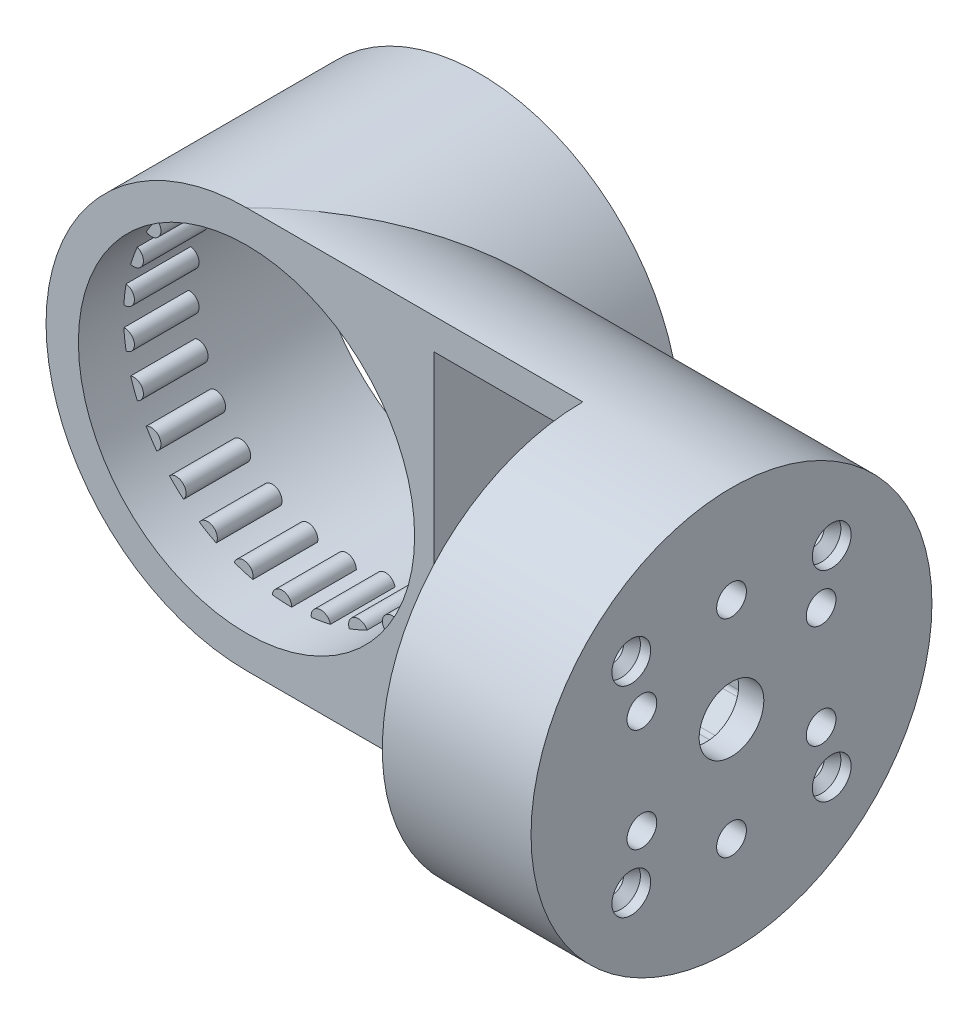
SolidWorks part; units mm, degrees
other "Markup1"
sketch "Sketch32" plane through (-30, -30, -30.9487) normal (-0.8677, -0.0705, -0.492) x (-0.0857, 0.9963, 0.0084)
ref_plane "Front Plane" through (0, 0, 0) normal (0, 0, 1) x (1, 0, 0)
ref_plane "Top Plane" through (0, 0, 0) normal (0, 1, 0) x (1, 0, 0)
ref_plane "Right Plane" through (0, 0, 0) normal (1, 0, 0) x (0, 0, -1)
sketch "Sketch3" plane through (0, 0, -2.9591) normal (0, 0, 1) x (1, 0, 0)
  circle A0 centre (0, 0) radius 31
  circle A1 centre (0, 0) radius 26
extrude "Boss-Extrude1" add sketch "Sketch3" along normal blind 7
sketch "Sketch4" plane through (0, 0, 4.0409) normal (0, 0, 1) x (1, 0, 0)
  line L0 (0, 0) -> (26, 0) construction
  circle A0 centre (0, 0) radius 26
  circle A1 centre (0, 0) radius 31
extrude "Boss-Extrude2" add sketch "Sketch4" along normal blind 10
sketch "Sketch5" plane through (0, 0, 4.0513) normal (0, 0, 1) x (1, 0, 0)
  line L0 (0, 0) -> (26, 0) construction
  circle A0 centre (0, 0) radius 26 construction
  circle A1 centre (26, 0) radius 1.5
  circle A2 centre (25.2992, -5.996) radius 1.5
  circle A3 centre (23.2344, -11.6688) radius 1.5
  circle A4 centre (19.9172, -16.7125) radius 1.5
  circle A5 centre (15.5261, -20.8552) radius 1.5
  circle A6 centre (10.2981, -23.8736) radius 1.5
  circle A7 centre (4.5149, -25.605) radius 1.5
  circle A8 centre (-1.5118, -25.956) radius 1.5
  circle A9 centre (-7.4569, -24.9077) radius 1.5
  circle A10 centre (-13, -22.5167) radius 1.5
  circle A11 centre (-17.8423, -18.9117) radius 1.5
  circle A12 centre (-21.7227, -14.2872) radius 1.5
  circle A13 centre (-24.432, -8.8925) radius 1.5
  circle A14 centre (-25.8242, -3.0184) radius 1.5
  circle A15 centre (-25.8242, 3.0184) radius 1.5
  circle A16 centre (-24.432, 8.8925) radius 1.5
  circle A17 centre (-21.7227, 14.2872) radius 1.5
  circle A18 centre (-17.8423, 18.9117) radius 1.5
  circle A19 centre (-13, 22.5167) radius 1.5
  circle A20 centre (-7.4569, 24.9077) radius 1.5
  circle A21 centre (-1.5118, 25.956) radius 1.5
  circle A22 centre (4.5149, 25.605) radius 1.5
  circle A23 centre (10.2981, 23.8736) radius 1.5
  circle A24 centre (15.5261, 20.8552) radius 1.5
  circle A25 centre (19.9172, 16.7125) radius 1.5
  circle A26 centre (23.2344, 11.6688) radius 1.5
  circle A27 centre (25.2992, 5.996) radius 1.5
  point P29 (0, 0)
  dimension "D1" = 27
extrude "Boss-Extrude3" add sketch "Sketch5" along normal blind 10
sketch "Sketch7" plane through (0, 0, 14.0409) normal (0, 0, 1) x (1, 0, 0)
  circle A0 centre (0, 0) radius 31
  circle A1 centre (0, 0) radius 26
extrude "Boss-Extrude4" add sketch "Sketch7" along normal blind 7
sketch "Sketch33" plane through (0, 0, -2.9591) normal (0, 0, -1) x (-1, 0, 0)
  circle A0 centre (0, 0) radius 26
  circle A1 centre (0, 0) radius 31
extrude "Boss-Extrude5" add sketch "Sketch33" along normal blind 12
ref_plane "Plane1" through (75, 0, 0) normal (1, 0, 0) x (0, 0, -1)
sketch "Sketch34" plane through (75, 0, 0) normal (1, 0, 0) x (0, 0, -1)
  line L2 (-21.0409, 31) -> (-21.0409, -31) construction
  line L3 (-21.0409, 31) -> (-21.0409, -31)
  arc A1 (-21.0409, -31) -> (-21.0409, 31) centre (-21.0409, 0) ccw
extrude "Boss-Extrude6" add sketch "Sketch34" against normal up to surface (75 mm away) up to face at (31, 0, 21.0409)
sketch "Sketch35" plane through (75, 0, 0) normal (1, 0, 0) x (0, 0, -1)
  line L2 (-21.0409, 31) -> (-21.0409, -31) construction
  line L3 (-21.0409, 31) -> (-21.0409, -31)
  arc A1 (-21.0409, 31) -> (-21.0409, -31) centre (-21.0409, 0) ccw
extrude "Boss-Extrude7" add sketch "Sketch35" against normal blind 23
sketch "Sketch37" plane through (52, 0, 0) normal (-1, 0, 0) x (0, 0, 1)
  line L2 (37.7892, 21.2058) -> (36.4277, 21.2058)
  line L3 (41.951, 17.4624) -> (38.5033, 20.91)
  line L4 (42.2467, 15.3868) -> (42.2467, 16.7483)
  line L5 (42.2467, -16.7483) -> (42.2467, -15.3868)
  line L6 (38.5033, -20.91) -> (41.951, -17.4624)
  line L7 (36.4277, -21.2058) -> (37.7892, -21.2058)
  line L33 (5.6541, -21.2058) -> (4.2926, -21.2058)
  line L34 (3.5786, -20.91) -> (0.1309, -17.4624)
  line L35 (-0.1649, -16.7483) -> (-0.1649, -15.3868)
  line L36 (-0.1649, 15.3868) -> (-0.1649, 16.7483)
  line L37 (0.1309, 17.4624) -> (3.5786, 20.91)
  line L38 (4.2926, 21.2058) -> (5.6541, 21.2058)
  arc A0 (37.7892, 21.2058) -> (38.5033, 20.91) centre (37.7892, 20.196) cw
  arc A1 (41.951, 17.4624) -> (42.2467, 16.7483) centre (41.2369, 16.7483) cw
  arc A2 (42.2467, 15.3868) -> (42.2467, -15.3868) centre (21.0409, 0) cw
  arc A3 (42.2467, -16.7483) -> (41.951, -17.4624) centre (41.2369, -16.7483) cw
  arc A4 (38.5033, -20.91) -> (37.7892, -21.2058) centre (37.7892, -20.196) cw
  arc A32 (5.6541, -21.2058) -> (36.4277, -21.2058) centre (21.0409, 0) ccw
  arc A33 (3.5786, -20.91) -> (4.2926, -21.2058) centre (4.2926, -20.196) ccw
  arc A34 (-0.1649, -16.7483) -> (0.1309, -17.4624) centre (0.8449, -16.7483) ccw
  arc A35 (-0.1649, 15.3868) -> (-0.1649, -15.3868) centre (21.0409, 0) ccw
  arc A36 (0.1309, 17.4624) -> (-0.1649, 16.7483) centre (0.8449, 16.7483) ccw
  arc A37 (4.2926, 21.2058) -> (3.5786, 20.91) centre (4.2926, 20.196) ccw
  arc A38 (36.4277, 21.2058) -> (5.6541, 21.2058) centre (21.0409, 0) ccw
extrude "Cut-Extrude1" cut sketch "Sketch37" against normal blind 23
sketch "Sketch38" plane through (52, 0, 0) normal (-1, 0, 0) x (0, 0, 1)
  line L9 (21.0409, 26.2) -> (21.0409, -26.2)
  line L10 (4.2926, 21.2058) -> (5.6541, 21.2058)
  line L37 (5.6541, -21.2058) -> (4.2926, -21.2058)
  line L39 (3.5786, -20.91) -> (0.1309, -17.4624)
  line L41 (-0.1649, -16.7483) -> (-0.1649, -15.3868)
  line L43 (-0.1649, 15.3868) -> (-0.1649, 16.7483)
  line L45 (0.1309, 17.4624) -> (3.5786, 20.91)
  arc A4 (5.6541, -21.2058) -> (21.0409, -26.2) centre (21.0409, 0) ccw
  arc A5 (21.0409, 26.2) -> (5.6541, 21.2058) centre (21.0409, 0) ccw
  arc A12 (3.5786, -20.91) -> (4.2926, -21.2058) centre (4.2926, -20.196) ccw
  arc A26 (-0.1649, -16.7483) -> (0.1309, -17.4624) centre (0.8449, -16.7483) ccw
  arc A28 (-0.1649, 15.3868) -> (-0.1649, -15.3868) centre (21.0409, 0) ccw
  arc A30 (0.1309, 17.4624) -> (-0.1649, 16.7483) centre (0.8449, 16.7483) ccw
  arc A32 (4.2926, 21.2058) -> (3.5786, 20.91) centre (4.2926, 20.196) ccw
  point P22 (-9.9591, 26.2)
  point P46 (-9.9591, -26.2)
extrude "Cut-Extrude2" cut sketch "Sketch38" along normal blind 23
sketch "Sketch39" plane through (75, 0, 0) normal (1, 0, 0) x (0, 0, -1)
  circle A0 centre (-21.0409, 0) radius 5
  circle A1 centre (-34.8973, -8) radius 2.3
  circle A2 centre (-5.5409, 15.5) radius 3
  circle A3 centre (-21.0409, -16) radius 2.3
  circle A4 centre (-7.1845, -8) radius 2.3
  circle A5 centre (-7.1845, 8) radius 2.3
  circle A6 centre (-21.0409, 16) radius 2.3
  circle A7 centre (-34.8973, 8) radius 2.3
  circle A8 centre (-5.5409, -15.5) radius 3
  circle A9 centre (-36.5409, -15.5) radius 3
  circle A10 centre (-36.5409, 15.5) radius 3
  dimension "D1" = 6
  dimension "D2" = 4
sketch "Sketch42" plane through (75, 0, 0) normal (1, 0, 0) x (0, 0, -1)
  line L0 (-21.0409, -26.2) -> (-21.0409, 26.2) construction
  circle A0 centre (-21.0409, 0) radius 31
extrude "Boss-Extrude8" add sketch "Sketch42" against normal blind 6
sketch "Sketch40" plane through (69, 0, 0) normal (-1, 0, 0) x (0, 0, 1)
  line L0 (21.0409, -31) -> (21.0409, 31) construction
  circle A1 centre (21.0409, 0) radius 11
extrude "Cut-Extrude3" cut sketch "Sketch40" against normal blind 2.1
extrude "Cut-Extrude4" cut sketch "Sketch39" against normal up to next
ref_point "Point1"
ref_point "Point2"
ref_plane "Plane2" through (0, 0, 36.5409) normal (0, 0, -1) x (-1, 0, 0)
sketch "Sketch41" plane through (0, 0, 36.5409) normal (0, 0, -1) x (-1, 0, 0)
  line L2 (-72.115, 17.2) -> (-73.415, 18.5)
  line L4 (-72.115, 17.2) -> (-69, 17.2)
  line L5 (-73.415, 18.5) -> (-69, 18.5)
  line L6 (-69, 18.5) -> (-69, 17.2)
ref_axis "Axis2" through (69, 15.5, 36.5409) along (1, 0, 0)
revolve "Revolve1" add sketch "Sketch41" angle 360 about axis through (69, 15.5, 36.5409) along (1, 0, 0)
pattern_circular "CirPattern1" count 4 over 360 about axis through (75, 0, 21.0409) along (1, 0, 0) of "Revolve1"
